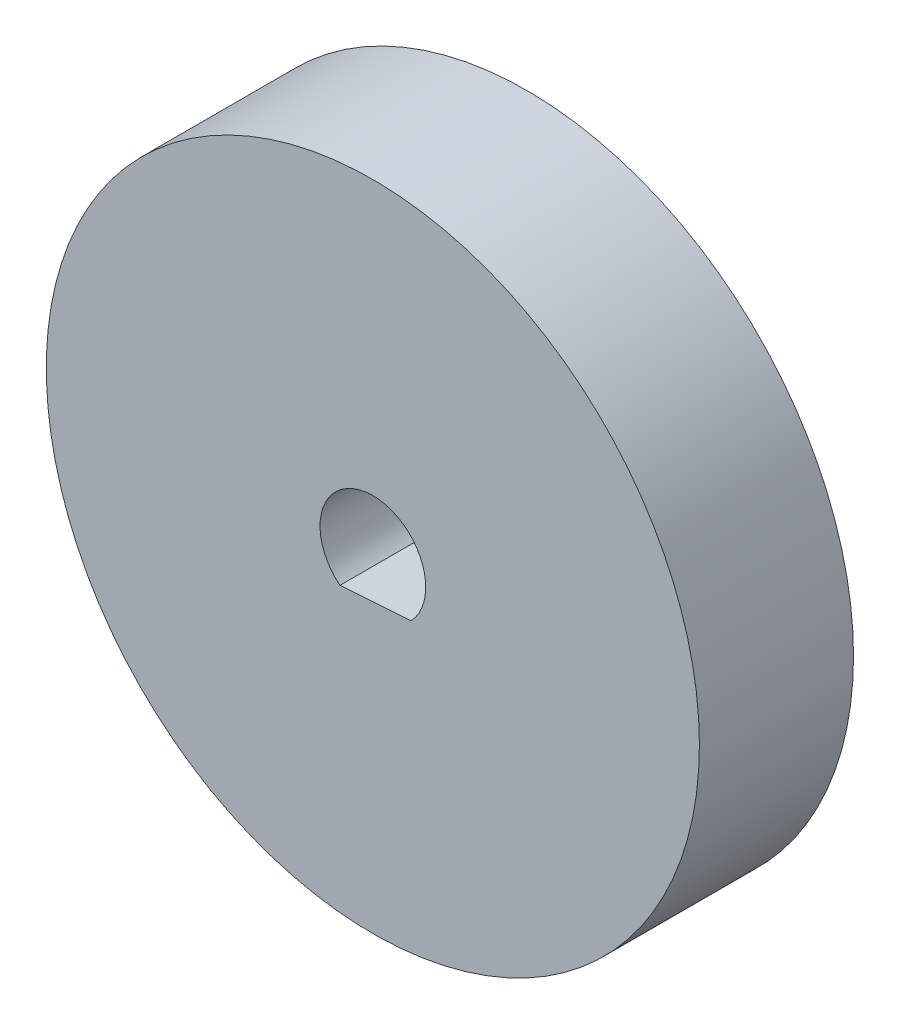
SolidWorks part; units mm, degrees
ref_plane "Front Plane" through (0, 0, 0) normal (0, 0, 1) x (1, 0, 0)
ref_plane "Top Plane" through (0, 0, 0) normal (0, 1, 0) x (1, 0, 0)
ref_plane "Right Plane" through (0, 0, 0) normal (1, 0, 0) x (0, 0, -1)
sketch "Sketch1" plane through (0, 0, 0) normal (0, 0, 1) x (1, 0, 0)
  circle A0 centre (0, 7.2896) radius 11.303
  dimension "D1" = 22.606
extrude "Boss-Extrude1" add sketch "Sketch1" along normal blind 5.334
sketch "Sketch2" plane through (0, 0, 0) normal (0, 0, -1) x (-1, 0, 0)
  line L1 (-1.3238, 6.0278) -> (1.1378, 5.8578)
  circle A0 centre (0, 7.2896) radius 1.8288
  circle A1 centre (0, 7.2896) radius 11.303 construction
  dimension "D1" = 3.6576
  dimension "D3" = 0
  dimension "D2" = 1.35
extrude "Cut-Extrude1" cut sketch "Sketch2" against normal through all contours L1 A0 region at (-0.0089, 7.4184, 0)
equation "\"MDF\"= .21in"
equation "\"Foamcore\"= .13in"
equation "\"Gmaterial\"= \"MDF\""
equation "\"D1@Boss-Extrude1\"=\"MDF\""
